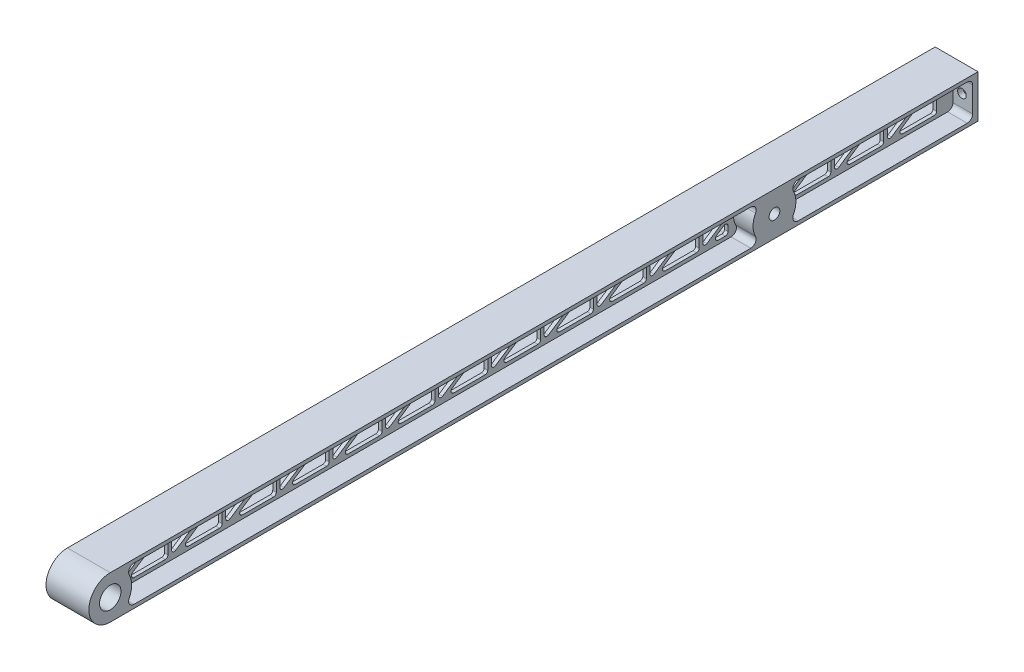
SolidWorks part; units mm, degrees
material "6061 Alloy"
ref_plane "Front Plane" through (0, 0, 0) normal (0, 0, 1) x (1, 0, 0)
ref_plane "Top Plane" through (0, 0, 0) normal (0, 1, 0) x (1, 0, 0)
ref_plane "Right Plane" through (0, 0, 0) normal (1, 0, 0) x (0, 0, -1)
sketch "Sketch1" plane through (0, 0, 0) normal (1, 0, 0) x (0, 0, -1)
  line L0 (0, 12.7) -> (514.35, 12.7)
  line L1 (0, -12.7) -> (514.35, -12.7)
  line L2 (514.35, 12.7) -> (514.35, 28.575) construction
  line L3 (514.35, 28.575) -> (520.7, 28.575) construction
  line L4 (520.7, 28.575) -> (520.7, -28.575) construction
  line L5 (520.7, -28.575) -> (514.35, -28.575) construction
  line L6 (514.35, -28.575) -> (514.35, -12.7) construction
  line L7 (514.35, 19.05) -> (558.8, 19.05) construction
  line L8 (558.8, 19.05) -> (558.8, -19.05) construction
  line L9 (558.8, -19.05) -> (514.35, -19.05) construction
  line L10 (514.35, 12.7) -> (514.35, -12.7)
  circle A0 centre (0, 0) radius 6.35
  arc A1 (0, -12.7) -> (0, 12.7) centre (0, 0) cw
  circle A4 centre (558.8, 0) radius 6.35 construction
  point P17 (520.7, 0)
  dimension "D1" = 12.7
  dimension "D2" = 12.7
  dimension "D6" = 38.1
  dimension "D3" = 6.35
  dimension "D4" = 57.15
  dimension "D7" = 558.8
  dimension "D8" = 25.4
  dimension "D9" = 38.1
extrude "Boss-Extrude1" add sketch "Sketch1" along normal blind 25.4
hole_wizard "1/4-20 Tapped Hole1" positions "Sketch3" profile "Sketch2" tap size "1/4-20" standard "ANSI Inch"
sketch "Sketch3" plane through (0, 0, -514.35) normal (0, 0, -1) x (-1, 0, 0)
  line L0 (0, 0) -> (-6.35, 0) construction
  line L2 (-6.35, 0) -> (-19.05, 0) construction
  line L3 (-19.05, 0) -> (-25.4, 0) construction
  line L5 (0, -12.7) -> (0, 12.7) construction
  line L6 (-25.4, -12.7) -> (-25.4, 12.7) construction
  point P13 (-6.35, 0)
  point P15 (-19.05, 0)
  dimension "D1" = 12.7
sketch "Sketch2" plane through (6.35, 0, -514.35) normal (1, 0, 0) x (0, 1, 0)
  line L0 (0, 0) -> (0, 18.0438)
  line L1 (0, 18.0438) -> (2.5527, 16.51)
  line L2 (2.5527, 16.51) -> (2.5527, 0)
  line L5 (2.5527, 0) -> (0, 0)
  line L10 (0, 18.0438) -> (-2.5527, 16.51) construction
  line L11 (0, -6.35) -> (0, 107.95) construction
  dimension "Tap Drill Dia." = 5.1054
  dimension "Tap Drill Depth" = 16.51
  dimension "Drill Angle" = 118
sketch "Sketch4" plane through (25.4, 0, 0) normal (1, 0, 0) x (0, 0, -1)
  line L0 (0, 0) -> (393.7, 0) construction
  circle A0 centre (393.7, 0) radius 3.175
  dimension "D1" = 6.35
  dimension "D2" = 393.7
extrude "Cut-Extrude1" cut sketch "Sketch4" against normal blind 38.1
sketch "Sketch5" plane through (0, 0, 0) normal (1, 0, 0) x (0, 0, -1)
  line L0 (0, 12.7) -> (0, 10.5833) construction
  line L1 (0, -12.7) -> (0, -10.5834) construction
  line L2 (393.7, -12.7) -> (393.7, -10.5834) construction
  line L3 (393.7, 12.7) -> (393.7, 10.5834) construction
  line L4 (393.7, 10.5834) -> (0, 10.5833)
  line L5 (0, -10.5834) -> (393.7, -10.5834)
  line L6 (12.7, 0) -> (15.875, 0) construction
  line L7 (15.875, 0) -> (15.875, 8.4667)
  line L8 (15.875, 0) -> (15.875, -8.4667)
  line L9 (15.875, -8.4667) -> (41.275, 8.4667)
  line L10 (15.875, 8.4667) -> (41.275, 8.4667)
  line L11 (28.575, 0) -> (29.9861, -2.1166) construction
  line L12 (29.9861, -2.1166) -> (45.8609, 8.4667)
  line L13 (29.9861, -2.1166) -> (20.4609, -8.4667)
  line L14 (20.4609, -8.4667) -> (45.8609, -8.4667)
  line L15 (45.8609, 8.4667) -> (45.8609, -8.4667)
  line L16 (45.8609, 8.4667) -> (47.9776, 8.4667) construction
  line L17 (47.9776, 8.4667) -> (47.9776, -8.4667)
  line L18 (47.9776, 8.4667) -> (73.3776, 8.4667)
  line L19 (47.9776, -8.4667) -> (73.3776, 8.4667)
  line L20 (60.6776, 0) -> (62.0886, -2.1166) construction
  line L21 (62.0886, -2.1166) -> (77.9635, 8.4667)
  line L22 (62.0886, -2.1166) -> (52.5635, -8.4667)
  line L23 (52.5635, -8.4667) -> (77.9635, -8.4667)
  line L24 (77.9635, -8.4667) -> (77.9635, 8.4667)
  line L25 (77.9635, 8.4667) -> (80.0802, 8.4667)
  line L26 (80.0802, 8.4667) -> (80.0802, -8.4667)
  line L27 (80.0802, 8.4667) -> (105.4802, 8.4667)
  line L28 (80.0802, -8.4667) -> (105.4802, 8.4667)
  line L29 (92.7802, 0) -> (94.1912, -2.1166)
  line L30 (94.1912, -2.1166) -> (84.6661, -8.4667)
  line L31 (94.1912, -2.1166) -> (110.0661, 8.4667)
  line L32 (84.6661, -8.4667) -> (110.0661, -8.4667)
  line L33 (110.0661, -8.4667) -> (110.0661, 8.4667)
  line L34 (110.0661, 8.4667) -> (112.1828, 8.4667) construction
  line L35 (112.1828, 8.4667) -> (112.1828, -8.4667)
  line L36 (112.1828, 8.4667) -> (137.5828, 8.4667)
  line L37 (112.1828, -8.4667) -> (137.5828, 8.4667)
  line L38 (124.8828, 0) -> (126.0569, -1.7612) construction
  line L39 (126.0569, -1.7612) -> (141.3986, 8.4667)
  line L40 (126.0569, -1.7612) -> (115.9986, -8.4667)
  line L41 (115.9986, -8.4667) -> (141.3986, -8.4667)
  line L42 (141.3986, -8.4667) -> (141.3986, 8.4667)
  line L43 (141.3986, 8.4667) -> (143.5153, 8.4667) construction
  line L44 (143.5153, 8.4667) -> (143.5153, -8.4667)
  line L45 (143.5153, 8.4667) -> (168.9153, 8.4667)
  line L46 (143.5153, -8.4667) -> (168.9153, 8.4667)
  line L47 (156.2153, 0) -> (157.3894, -1.7612)
  line L48 (157.3894, -1.7612) -> (172.7311, 8.4667)
  line L49 (157.3894, -1.7612) -> (147.3311, -8.4667)
  line L50 (147.3311, -8.4667) -> (172.7311, -8.4667)
  line L51 (172.7311, -8.4667) -> (172.7311, 8.4667)
  line L52 (172.7311, 8.4667) -> (174.8478, 8.4667) construction
  line L53 (174.8478, 8.4667) -> (174.8478, -8.4667)
  line L54 (174.8478, 8.4667) -> (200.2478, 8.4667)
  line L55 (174.8478, -8.4667) -> (200.2478, 8.4667)
  line L56 (187.5478, 0) -> (188.7219, -1.7612) construction
  line L57 (188.7219, -1.7612) -> (204.0637, 8.4667)
  line L58 (188.7219, -1.7612) -> (178.6637, -8.4667)
  line L59 (178.6637, -8.4667) -> (204.0637, -8.4667)
  line L60 (204.0637, -8.4667) -> (204.0637, 8.4667)
  line L61 (204.0637, 8.4667) -> (206.1802, 8.4667) construction
  line L62 (206.1802, 8.4667) -> (206.1802, -8.4667)
  line L63 (206.1802, 8.4667) -> (231.5802, 8.4667)
  line L64 (231.5802, 8.4667) -> (206.1802, -8.4667)
  line L65 (218.8802, 0) -> (220.0544, -1.7612) construction
  line L66 (220.0544, -1.7612) -> (235.3961, 8.4667)
  line L67 (220.0544, -1.7612) -> (209.9961, -8.4667)
  line L68 (209.9961, -8.4667) -> (235.3961, -8.4667)
  line L69 (235.3961, -8.4667) -> (235.3961, 8.4667)
  line L70 (235.3961, 8.4667) -> (237.5128, 8.4667) construction
  line L71 (237.5128, 8.4667) -> (237.5128, -8.4667)
  line L72 (237.5128, 8.4667) -> (262.9128, 8.4667)
  line L73 (262.9128, 8.4667) -> (237.5128, -8.4667)
  line L74 (250.2128, 0) -> (251.3869, -1.7612) construction
  line L75 (251.3869, -1.7612) -> (266.7286, 8.4667)
  line L76 (251.3869, -1.7612) -> (241.3286, -8.4667)
  line L77 (241.3286, -8.4667) -> (266.7286, -8.4667)
  line L78 (266.7286, -8.4667) -> (266.7286, 8.4667)
  line L79 (266.7286, 8.4667) -> (268.8453, 8.4667) construction
  line L80 (268.8453, 8.4667) -> (268.8453, -8.4667)
  line L81 (268.8453, 8.4667) -> (294.2453, 8.4667)
  line L82 (294.2453, 8.4667) -> (268.8453, -8.4667)
  line L83 (281.5453, 0) -> (282.7194, -1.7612) construction
  line L84 (282.7194, -1.7612) -> (298.0612, 8.4667)
  line L85 (282.7194, -1.7612) -> (272.6612, -8.4667)
  line L86 (272.6612, -8.4667) -> (298.0612, -8.4667)
  line L87 (298.0612, -8.4667) -> (298.0612, 8.4667)
  line L88 (298.0612, 8.4667) -> (300.1778, 8.4667) construction
  line L89 (300.1778, 8.4667) -> (300.1778, -8.4667)
  line L90 (300.1778, 8.4667) -> (325.5778, 8.4667)
  line L91 (325.5778, 8.4667) -> (300.1778, -8.4667)
  line L92 (312.8778, 0) -> (314.0519, -1.7612) construction
  line L93 (314.0519, -1.7612) -> (329.3937, 8.4667)
  line L94 (314.0519, -1.7612) -> (303.9937, -8.4667)
  line L95 (303.9937, -8.4667) -> (329.3937, -8.4667)
  line L96 (329.3937, -8.4667) -> (329.3937, 8.4667)
  line L97 (329.3937, 8.4667) -> (331.5103, 8.4667) construction
  line L98 (331.5103, 8.4667) -> (331.5103, -8.4667)
  line L99 (331.5103, 8.4667) -> (356.9103, 8.4667)
  line L100 (331.5103, -8.4667) -> (356.9103, 8.4667)
  line L101 (344.2103, 0) -> (345.3844, -1.7612) construction
  line L102 (345.3844, -1.7612) -> (360.7262, 8.4667)
  line L103 (345.3844, -1.7612) -> (335.3262, -8.4667)
  line L104 (335.3262, -8.4667) -> (360.7262, -8.4667)
  line L105 (360.7262, -8.4667) -> (360.7262, 8.4667)
  line L106 (360.7262, 8.4667) -> (362.8429, 8.4667)
  line L107 (362.8429, 8.4667) -> (362.8429, -8.4667)
  line L108 (514.35, 12.7) -> (511.175, 12.7)
  line L109 (377.825, 1.5214) -> (377.825, 8.4667)
  line L110 (377.825, -1.0225) -> (377.825, -8.4667)
  line L111 (362.8429, 8.4667) -> (377.825, 8.4667)
  line L112 (377.825, 1.5214) -> (362.8429, -8.4667)
  line L113 (370.3339, -3.4726) -> (371.508, -5.2338) construction
  line L114 (371.508, -5.2338) -> (377.825, -1.0225)
  line L115 (371.508, -5.2338) -> (366.6587, -8.4667)
  line L116 (366.6587, -8.4667) -> (377.825, -8.4667)
  line L117 (514.35, 12.7) -> (0, 12.7) construction
  line L118 (511.175, 12.7) -> (511.175, -12.7)
  line L119 (0, -12.7) -> (514.35, -12.7) construction
  line L120 (393.7, 10.5834) -> (514.35, 10.5834)
  line L121 (514.35, -12.7) -> (514.35, 12.7) construction
  line L122 (393.7, -10.5834) -> (514.35, -10.5834)
  line L123 (406.4, 0) -> (409.575, 0) construction
  line L124 (409.575, -8.4667) -> (409.575, 8.4667)
  line L125 (409.575, 8.4667) -> (434.975, 8.4667)
  line L126 (409.575, -8.4667) -> (434.975, 8.4667)
  line L127 (422.275, 0) -> (423.4491, -1.7612) construction
  line L128 (423.4491, -1.7612) -> (438.7909, 8.4667)
  line L129 (423.4491, -1.7612) -> (413.3909, -8.4667)
  line L130 (413.3909, -8.4667) -> (438.7909, -8.4667)
  line L131 (438.7909, -8.4667) -> (438.7909, 8.4667)
  line L132 (438.7909, 8.4667) -> (440.9075, 8.4667) construction
  line L133 (440.9075, 8.4667) -> (440.9075, -8.4667)
  line L134 (440.9075, 8.4667) -> (466.3075, 8.4667)
  line L135 (440.9075, -8.4667) -> (466.3075, 8.4667)
  line L136 (453.6075, 0) -> (454.7816, -1.7612) construction
  line L137 (454.7816, -1.7612) -> (470.1234, 8.4667)
  line L138 (454.7816, -1.7612) -> (444.7234, -8.4667)
  line L139 (444.7234, -8.4667) -> (470.1234, -8.4667)
  line L140 (470.1234, -8.4667) -> (470.1234, 8.4667)
  line L141 (470.1234, 8.4667) -> (472.24, 8.4667) construction
  line L142 (472.24, 8.4667) -> (472.24, -8.4667)
  line L143 (472.24, 8.4667) -> (497.64, 8.4667)
  line L144 (497.64, 8.4667) -> (472.24, -8.4667)
  line L145 (484.94, 0) -> (486.1142, -1.7612) construction
  line L146 (486.1142, -1.7612) -> (501.4559, 8.4667)
  line L147 (486.1142, -1.7612) -> (476.0559, -8.4667)
  line L148 (476.0559, -8.4667) -> (501.4559, -8.4667)
  line L149 (501.4559, -8.4667) -> (501.4559, 8.4667)
  circle A0 centre (0, 0) radius 12.7
  circle A1 centre (393.7, 0) radius 12.7
  dimension "D1" = 25.4
  dimension "D2" = 25.4
  dimension "D3" = 2.1166
  dimension "D4" = 2.1167
  dimension "D5" = 2.1166
  dimension "D6" = 2.1166
  dimension "D7" = 3.175
  dimension "D8" = 8.4667
  dimension "D9" = 8.4667
  dimension "D10" = 25.4
  dimension "D11" = 2.1166
  dimension "D12" = 25.4
  dimension "D13" = 2.1167
  dimension "D14" = 16.9333
  dimension "D15" = 25.4
  dimension "D16" = 2.1166
  dimension "D17" = 2.1167
  dimension "D18" = 25.4
  dimension "D19" = 16.9333
  dimension "D20" = 2.1166
  dimension "D21" = 2.1167
  dimension "D22" = 25.4
  dimension "D23" = 2.1167
  dimension "D24" = 2.1167
  dimension "D25" = 25.4
  dimension "D26" = 2.1167
  dimension "D27" = 2.1167
  dimension "D28" = 25.4
  dimension "D29" = 25.4
  dimension "D30" = 25.4
  dimension "D31" = 25.4
  dimension "D32" = 25.4
  dimension "D33" = 16.9333
  dimension "D34" = 25.4
  dimension "D35" = 16.9333
  dimension "D36" = 2.1166
  dimension "D37" = 25.4
  dimension "D38" = 2.1167
  dimension "D39" = 2.1167
  dimension "D40" = 2.1167
  dimension "D41" = 25.4
  dimension "D42" = 16.9333
  dimension "D43" = 2.1167
  dimension "D44" = 16.9333
  dimension "D45" = 2.1167
  dimension "D46" = 25.4
  dimension "D47" = 2.1167
  dimension "D48" = 2.1167
  dimension "D49" = 25.4
  dimension "D50" = 2.1167
  dimension "D51" = 25.4
  dimension "D52" = 2.1167
  dimension "D53" = 2.1167
  dimension "D54" = 3.175
  dimension "D55" = 2.1167
  dimension "D56" = 3.175
  dimension "D57" = 25.4
  dimension "D58" = 2.1167
  dimension "D59" = 2.1167
  dimension "D60" = 25.4
  dimension "D61" = 2.1167
  dimension "D62" = 2.1167
  dimension "D63" = 25.4
  dimension "D64" = 2.1167
  dimension "D65" = 2.1167
extrude "Cut-Extrude2" cut sketch "Sketch5" along normal blind 11.6417 contours A1 L4 A0 L5 L109 L112 L107 L105 L104 L103 L102 L111 L100 L98 L99 L96 L95 L94 L93 L81 L82 L80 L78 L77 L76 L75 L63 L64 L62 L60 L59 L58 L57 L55 L53 L54 L51 L50 L49 | A1 L122 L118 L120 L149 L148 L147 L146 L126 L124 L125 L131 L130 L129 L128 L135 L133 L134 L140 L139 L138 L137 L143 L144 L142 region at (0, 0, -377.1975) region at (0, 9.4588, -455.9475)
extrude "Cut-Extrude7" cut sketch "Sketch5<5>" along normal up to next (25.4 mm away) contours L112 L109 L111 L107 | L104 L105 L102 L103 | L98 L100 L99 | L95 L96 L93 L94 | L91 L90 L89 | L73 L72 L71 | L68 L69 L66 L67 | L64 L63 L62 | L59 L60 L57 L58 | L53 L55 L54 | L50 L51 L48 L49 | L44 L46 L45 | L41 L42 L39 L40 | L35 L37 L36 | L32 L33 L31 L30 | L26 L28 L27 | L115 L116 L110 L114 | L82 L81 L80 | L86 L87 L84 L85 | L77 L78 L75 L76 | L23 L24 L21 L22 | L17 L19 L18 | L15 L12 L13 L14 | L10 L7 L8 L9 | L124 L126 L125 | L130 L131 L128 L129 | L133 L135 L134 | L139 L140 L137 L138 | L144 L143 L142 | L148 L149 L146 L147 | L26 L28 L27 region at (0, 2.8222, -24.3417) region at (0, -2.8222, -37.3943) region at (0, 2.8222, -56.4443) region at (0, -2.8222, -101.5994) region at (0, 2.8222, -88.5468) region at (0, -2.8222, -69.4969) region at (0, 2.8222, -120.6494) region at (0, -2.8222, -132.932) region at (0, 2.8222, -151.982) region at (0, -2.8222, -164.2645) region at (0, 2.8222, -183.3145) region at (0, -2.8222, -195.597) region at (0, 2.8222, -214.6469) region at (0, -2.8222, -226.9294) region at (0, 2.8222, -245.9794) region at (0, -2.8222, -258.262) region at (0, 2.8222, -277.312) region at (0, -2.8222, -289.5945) region at (0, 2.8222, -308.6445) region at (0, -2.8222, -320.927) region at (0, 2.8222, -339.977) region at (0, 2.1489, -369.2895) region at (0, -2.8222, -352.2595) region at (0, -5.9853, -374.1029) region at (0, 2.8222, -418.0417) region at (0, -2.8222, -430.3242) region at (0, 2.8222, -449.3742) region at (0, -2.8222, -461.6567) region at (0, 2.8222, -480.7067) region at (0, -2.8222, -492.9892)
sketch "Sketch5<5>" plane through (0, 0, 0) normal (1, 0, 0) x (0, 0, -1) same geometry as "Sketch5"
sketch "Sketch16" plane through (25.4, 0, 0) normal (1, 0, 0) x (0, 0, -1)
  line L0 (393.7, 12.7) -> (393.7, 10.5833)
  line L1 (393.7, -12.7) -> (393.7, -10.5834)
  line L2 (0, 12.7) -> (0, 10.5833)
  line L3 (0, -12.7) -> (0, -10.5834)
  line L4 (0, -10.5834) -> (393.7, -10.5834)
  line L5 (393.7, 10.5833) -> (0, 10.5833)
  circle A0 centre (0, 0) radius 12.7
  circle A1 centre (393.7, 0) radius 12.7
  dimension "D1" = 25.4
  dimension "D2" = 25.4
  dimension "D3" = 2.1166
  dimension "D4" = 2.1167
extrude "Cut-Extrude8" cut sketch "Sketch16" against normal blind 11.6417 contours A1 L5 A0 L4 region at (25.4, 0, -196.85)
sketch "Sketch17" plane through (25.4, 0, 0) normal (1, 0, 0) x (0, 0, -1)
  line L0 (393.7, 12.7) -> (393.7, 10.5833)
  line L1 (393.7, -12.7) -> (393.7, -10.5834)
  line L2 (514.35, 12.7) -> (511.175, 12.7)
  line L3 (514.35, 12.7) -> (0, 12.7) construction
  line L4 (511.175, 12.7) -> (511.175, 10.5833)
  line L5 (514.35, -12.7) -> (511.175, -12.7)
  line L6 (0, -12.7) -> (514.35, -12.7) construction
  line L7 (511.175, -12.7) -> (511.175, -10.5834)
  line L8 (511.175, -10.5834) -> (393.7, -10.5834)
  line L9 (393.7, 10.5833) -> (511.175, 10.5833)
  line L10 (511.175, 10.5833) -> (511.175, -10.5834)
  circle A0 centre (393.7, 0) radius 12.7
  line M1 (501.4559, -8.4667) -> (476.0559, -8.4667)
  line M2 (476.0559, -8.4667) -> (501.4559, 8.4667)
  line M3 (501.4559, 8.4667) -> (501.4559, -8.4667)
  line M4 (472.24, 8.4667) -> (497.64, 8.4667)
  line M5 (497.64, 8.4667) -> (472.24, -8.4667)
  line M6 (472.24, -8.4667) -> (472.24, 8.4667)
  line M7 (440.9075, -8.4667) -> (440.9075, 8.4667)
  line M8 (440.9075, 8.4667) -> (466.3075, 8.4667)
  line M9 (466.3075, 8.4667) -> (440.9075, -8.4667)
  line M16 (434.975, 8.4667) -> (409.575, -8.4667)
  line M17 (409.575, -8.4667) -> (409.575, 8.4667)
  line M18 (409.575, 8.4667) -> (434.975, 8.4667)
  line M19 (438.7909, -8.4667) -> (413.3909, -8.4667)
  line M20 (413.3909, -8.4667) -> (438.7909, 8.4667)
  line M21 (438.7909, 8.4667) -> (438.7909, -8.4667)
  line M22 (470.1234, -8.4667) -> (444.7234, -8.4667)
  line M23 (444.7234, -8.4667) -> (470.1234, 8.4667)
  line M24 (470.1234, 8.4667) -> (470.1234, -8.4667)
  dimension "D1" = 25.4
  dimension "D2" = 3.175
  dimension "D3" = 2.1166
  dimension "D4" = 2.1167
  dimension "D5" = 2.1166
  dimension "D6" = 2.1167
  dimension "D7" = 3.175
extrude "Cut-Extrude9" cut sketch "Sketch17" against normal blind 11.6417 contours A0 L8 L10 L9 M6 M4 M5 M21 M19 M20 M24 M22 M23 M18 M16 M17 M9 M7 M8 M3 M1 M2 region at (25.4, 9.4587, -455.9476)
fillet "Fillet6" radius 1.5875 91 edges at (12.7, 1.5214, -377.825) (12.7, 8.4667, -377.825) (12.7, 8.4667, -362.8429) (12.7, -8.4667, -362.8429) (12.7, -8.4667, -335.3262) (12.7, -8.4667, -360.7262) (12.7, 8.4667, -360.7262) (12.7, 8.4667, -331.5103) (12.7, -8.4667, -331.5103) (12.7, 8.4667, -356.9103) (12.7, -8.4667, -303.9937) (12.7, -8.4667, -329.3937) (12.7, 8.4667, -329.3937) (12.7, 8.4667, -262.9128) (12.7, 8.4667, -237.5128) (12.7, -8.4667, -237.5128) (12.7, -8.4667, -209.9961) (12.7, -8.4667, -235.3961) (12.7, 8.4667, -235.3961) (12.7, 8.4667, -294.2453) (12.7, 8.4667, -268.8453) (12.7, -8.4667, -268.8453) (12.7, -8.4667, -272.6612) (12.7, -8.4667, -298.0612) (12.7, 8.4667, -298.0612) (12.7, -8.4667, -241.3286) (12.7, -8.4667, -266.7286) (12.7, 8.4667, -266.7286) (12.7, -8.4667, -52.5635) (12.7, -8.4667, -77.9635) (12.7, 8.4667, -77.9635) (12.7, 8.4667, -47.9776) (12.7, -8.4667, -47.9776) (12.7, 8.4667, -73.3776) (12.7, 8.4667, -15.875) (12.7, -8.4667, -15.875) (12.7, 8.4667, -41.275) (12.7, 8.4667, -45.8609) (12.7, -8.4667, -20.4609) (12.7, -8.4667, -45.8609) (12.7, -1.0225, -377.825) (12.7, -8.4667, -366.6587) (12.7, 8.4667, -80.0802) (12.7, -8.4667, -80.0802) (12.7, 8.4667, -105.4802) (12.7, -8.4667, -84.6661) (12.7, -8.4667, -110.0661) (12.7, 8.4667, -110.0661) (12.7, 8.4667, -112.1828) (12.7, -8.4667, -112.1828) (12.7, 8.4667, -137.5828) (12.7, -8.4667, -115.9986) (12.7, -8.4667, -141.3986) (12.7, 8.4667, -141.3986) (12.7, 8.4667, -143.5153) (12.7, -8.4667, -143.5153) (12.7, 8.4667, -168.9153) (12.7, -8.4667, -147.3311) (12.7, -8.4667, -172.7311) (12.7, 8.4667, -172.7311) (12.7, 8.4667, -174.8478) (12.7, -8.4667, -174.8478) (12.7, 8.4667, -200.2478) (12.7, -8.4667, -178.6637) (12.7, -8.4667, -204.0637) (12.7, 8.4667, -204.0637) (12.7, 8.4667, -231.5802) (12.7, 8.4667, -206.1802) (12.7, -8.4667, -206.1802) (12.7, 8.4667, -325.5778) (12.7, 8.4667, -300.1778) (12.7, -8.4667, -300.1778) (12.7, -8.4667, -377.825) (12.7, 8.4667, -501.4559) (12.7, -8.4667, -476.0559) (12.7, -8.4667, -501.4559) (12.7, 8.4667, -466.3075) (12.7, 8.4667, -440.9075) (12.7, -8.4667, -440.9075) (12.7, 8.4667, -470.1234) (12.7, -8.4667, -444.7234) (12.7, -8.4667, -470.1234) (12.7, 8.4667, -438.7909) (12.7, -8.4667, -413.3909) (12.7, -8.4667, -438.7909) (12.7, -8.4667, -472.24) (12.7, 8.4667, -497.64) (12.7, 8.4667, -472.24) (12.7, 8.4667, -434.975) (12.7, 8.4667, -409.575) (12.7, -8.4667, -409.575)
fillet "Fillet3" radius 3.175 16 edges at (5.8209, 10.5833, -7.0202) (5.8209, -10.5834, -7.0201) (19.5792, 10.5833, -7.0202) (19.5792, -10.5834, -7.0201) (19.5792, -10.5834, -386.6799) (19.5792, 10.5833, -386.6798) (5.8209, -10.5834, -386.6799) (5.8209, 10.5834, -386.6799) (19.5791, 10.5833, -400.7202) (19.5791, 10.5833, -511.175) (19.5791, -10.5834, -511.175) (19.5791, -10.5834, -400.7201) (5.8209, -10.5834, -400.7201) (5.8209, -10.5834, -511.175) (5.8209, 10.5834, -511.175) (5.8209, 10.5834, -400.7201)
